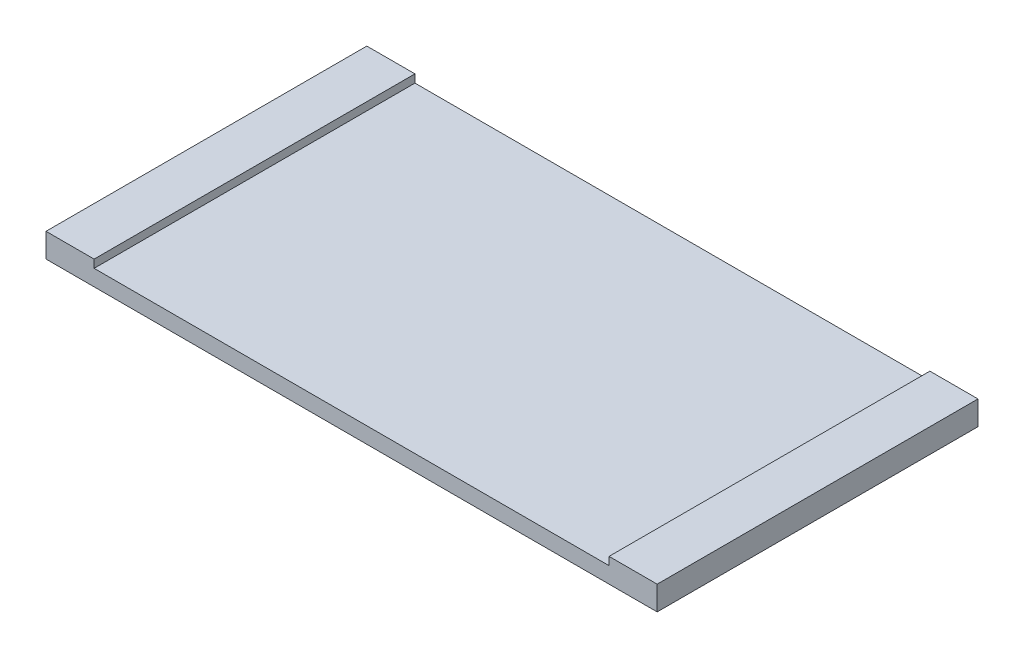
SolidWorks part; units mm, degrees
ref_plane "Front Plane" through (0, 0, 0) normal (0, 0, 1) x (1, 0, 0)
ref_plane "Top Plane" through (0, 0, 0) normal (0, 1, 0) x (1, 0, 0)
ref_plane "Right Plane" through (0, 0, 0) normal (1, 0, 0) x (0, 0, -1)
sketch "Sketch1" plane through (0, 0, 0) normal (0, 1, 0) x (1, 0, 0)
  line L1 (0, 0) -> (76.2, 0)
  line L2 (0, 0) -> (0, 40)
  line L3 (0, 40) -> (76.2, 40)
  line L4 (76.2, 0) -> (76.2, 40)
  dimension "D1" = 76.2
  dimension "D2" = 40
extrude "Boss-Extrude1" add sketch "Sketch1" along normal blind 3
sketch "Sketch2" plane through (0, 3, 0) normal (0, 1, 0) x (1, 0, 0)
  line L0 (76.2, 40) -> (0, 40) construction
  line L1 (6, 40) -> (70.2, 40)
  line L2 (6, 40) -> (6, 0)
  line L3 (6, 0) -> (70.2, 0)
  line L4 (70.2, 40) -> (70.2, 0)
  line L5 (0, 0) -> (76.2, 0) construction
  line L6 (0, 40) -> (0, 0) construction
  line L7 (76.2, 0) -> (76.2, 40) construction
  dimension "D1" = 6
  dimension "D2" = 6
extrude "Cut-Extrude1" cut sketch "Sketch2" against normal blind 1
